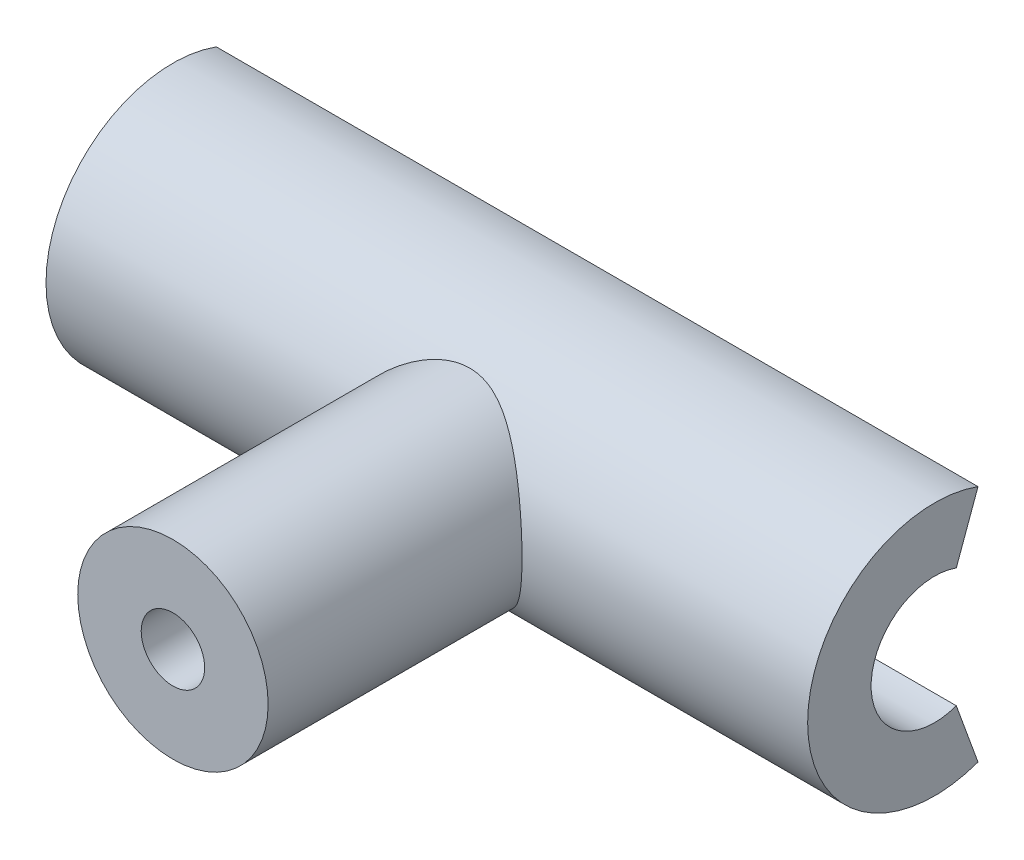
SolidWorks part; units mm, degrees
ref_plane "Front Plane" through (0, 0, 0) normal (0, 0, 1) x (1, 0, 0)
ref_plane "Top Plane" through (0, 0, 0) normal (0, 1, 0) x (1, 0, 0)
ref_plane "Right Plane" through (0, 0, 0) normal (1, 0, 0) x (0, 0, -1)
sketch "Sketch1" plane through (0, 0, 0) normal (0, 0, 1) x (1, 0, 0)
  circle A0 centre (0, 0) radius 0.7937
  circle A1 centre (0, 0) radius 2.3812
  dimension "D1" = 1.5875
  dimension "D2" = 1.5875
extrude "Boss-Extrude1" add sketch "Sketch1" along normal blind 9.525
sketch "Sketch2" plane through (0, 0, 0) normal (0, 1, 0) x (1, 0, 0)
  line L0 (0, 0) -> (-9.525, 0)
  line L1 (2.3812, 0) -> (-2.3812, 0) construction
  dimension "D1" = 9.525
ref_plane "Plane1" through (-9.525, 0, 0) normal (-1, 0, 0) x (0, 0, 1)
sketch "Sketch3" plane through (-9.525, 0, 0) normal (-1, 0, 0) x (0, 0, 1)
  line L0 (-1.0859, -2.9835) -> (-0.543, -1.4918)
  line L1 (-0.543, 1.4918) -> (-1.0859, 2.9835)
  line L2 (0, 0) -> (0, 3.175) construction
  line L3 (0, 0) -> (0, -3.175) construction
  line L4 (0, 0) -> (-0.543, 1.4918) construction
  line L5 (-0.543, -1.4918) -> (0, 0) construction
  arc A0 (-1.0859, 2.9835) -> (-1.0859, -2.9835) centre (0, 0) cw
  arc A1 (-0.543, -1.4918) -> (-0.543, 1.4918) centre (0, 0) ccw
  dimension "D1" = 20
  dimension "D2" = 3.175
  dimension "D4" = 1.5875
  dimension "D3" = 20
extrude "Boss-Extrude2" add sketch "Sketch3" against normal blind 19.05
sketch "Sketch4" plane through (-9.525, 0, 0) normal (-1, 0, 0) x (0, 0, 1)
  circle A0 centre (0, 0) radius 1.5875
extrude "Cut-Extrude1" cut sketch "Sketch4" against normal through all
